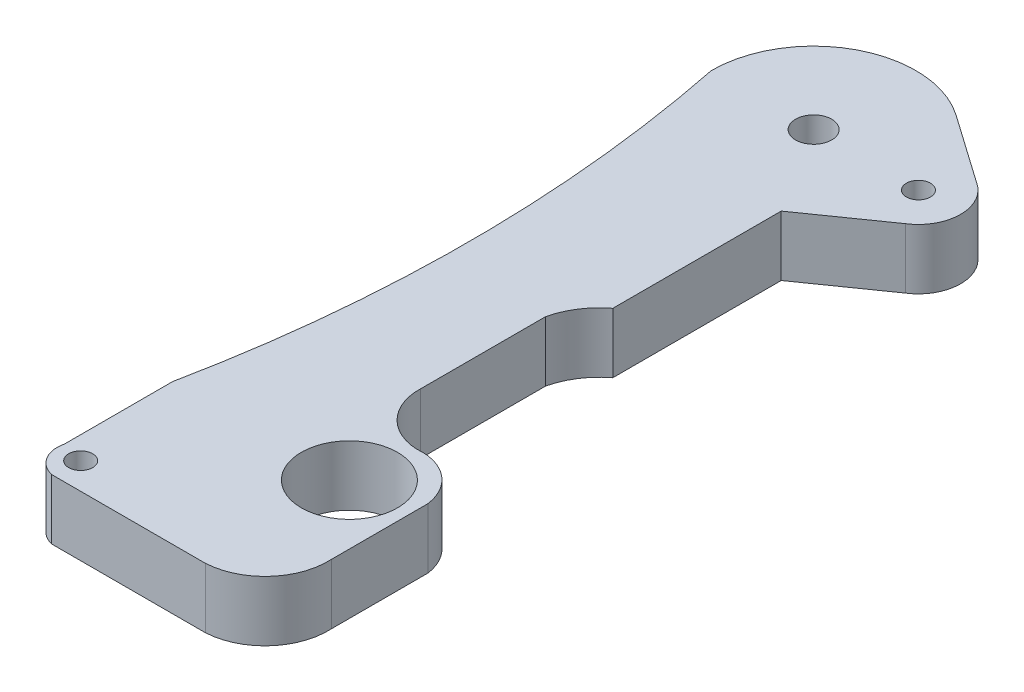
SolidWorks part; units mm, degrees
ref_plane "Front Plane" through (0, 0, 0) normal (0, 0, 1) x (1, 0, 0)
ref_plane "Top Plane" through (0, 0, 0) normal (0, 1, 0) x (1, 0, 0)
ref_plane "Right Plane" through (0, 0, 0) normal (1, 0, 0) x (0, 0, -1)
sketch "Sketch1" plane through (0, 0, 0) normal (0, 1, 0) x (1, 0, 0)
  line L0 (98.4251, 42.5572) -> (140.2114, 42.5572) construction
  line L1 (35.0753, 78.1982) -> (40.7853, 74.193)
  line L2 (40.7853, 68.2859) -> (34.7132, 64.0267)
  line L3 (34.7132, 64.0267) -> (34.7132, 50.0267)
  line L6 (23.3425, 14.7395) -> (33.8413, 14.7395)
  line L7 (41.0908, 20.2711) -> (41.0908, 28.2863)
  line L8 (32.5197, 36.2541) -> (32.5197, 46.64)
  line L9 (36.7123, 31.7391) -> (31.3478, 31.7391) construction
  line L10 (33.8413, 14.7395) -> (41.0908, 14.7395) construction
  line L11 (21.6941, 17.4633) -> (21.6941, 26.4633)
  line L12 (33.8413, 14.7395) -> (36.1322, 14.7395)
  arc A0 (35.0753, 78.1982) -> (21.6941, 71.2395) centre (30.1941, 71.2395) ccw
  circle A1 centre (30.1941, 71.2395) radius 1.5
  circle A2 centre (38.9073, 71.2395) radius 1
  arc A5 (41.0908, 28.2863) -> (36.7123, 31.7391) centre (37.1255, 27.7605) ccw
  circle A8 centre (23.5664, 16.9435) radius 1
  circle A9 centre (36.1322, 26.7162) radius 4
  arc A10 (38.6393, 70.2761) -> (38.6393, 72.2029) centre (30.1941, 71.2395) ccw
  arc A11 (40.7853, 68.2859) -> (40.7853, 74.193) centre (38.9073, 71.2395) ccw
  arc A13 (36.7123, 31.7391) -> (32.5197, 36.2541) centre (36.8735, 36.0929) cw
  arc A14 (21.6941, 17.4633) -> (23.3425, 14.7395) centre (23.8802, 16.9256) ccw
  arc A15 (21.6941, 71.2395) -> (21.6941, 26.4633) centre (-88.6742, 48.8514) cw
  arc A16 (32.5197, 46.64) -> (34.7132, 50.0267) centre (38.3165, 45.2893) cw
  arc A17 (36.1322, 14.7395) -> (41.0908, 20.2711) centre (35.8457, 19.9846) ccw
  point P7 (30.1941, 79.7395)
  point P35 (21.9542, 15.76)
  dimension "D2" = 8.5
  dimension "D3" = 3.5
  dimension "D4" = 3
  dimension "D5" = 2
  dimension "D7" = 8
  dimension "D8" = 4
  dimension "D9" = 2
  dimension "D1" = 65
  dimension "D6" = 14
  dimension "D10" = 2
  dimension "D11" = 9
extrude "Boss-Extrude1" add sketch "Sketch1" along normal blind 5 contours L12 A17 L7 A5 A13 L8 A16 L3 L2 A11 L1 A0 A15 L11 A14 L6 A1 A2 A8 A9 region at (29.9187, 0, -46.9295)
